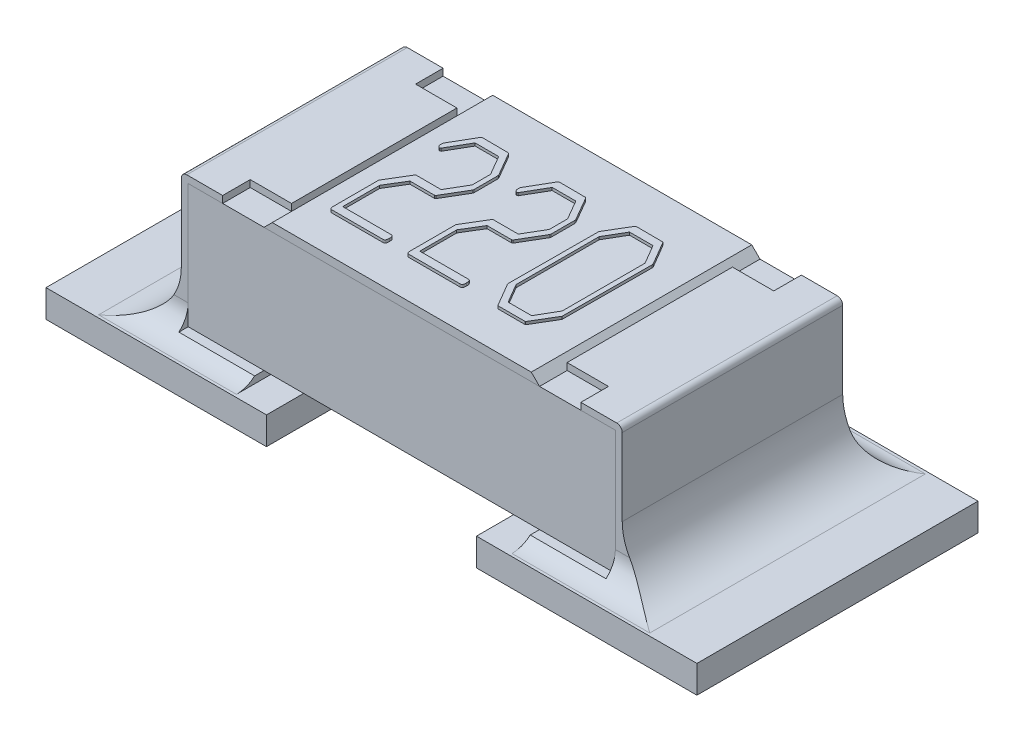
SolidWorks part; units mm, degrees
material "Ceramic Porcelain"
ref_plane "Front Plane" through (0, 0, 0) normal (0, 0, 1) x (1, 0, 0)
ref_plane "Top Plane" through (0, 0, 0) normal (0, 1, 0) x (1, 0, 0)
ref_plane "Right Plane" through (0, 0, 0) normal (1, 0, 0) x (0, 0, -1)
sketch "Sketch1" plane through (0, 0, 0) normal (1, 0, 0) x (0, 0, -1)
  line L0 (0, 55) -> (0, -55) construction
  line L1 (-0.4, 0.575) -> (0.4, 0.575)
  line L2 (-0.4, 0.575) -> (-0.4, 0.125)
  line L3 (-0.4, 0.125) -> (0.4, 0.125)
  line L4 (0.4, 0.575) -> (0.4, 0.125)
  line L5 (55, 0) -> (-55, 0) construction
  dimension "D1" = 0.8
  dimension "D2" = 0.4
  dimension "D3" = 0.45
  dimension "D4" = 0.125
extrude "Boss-Extrude1" add sketch "Sketch1" along normal mid plane 1.55
sketch "Sketch2" plane through (0, 0, 0) normal (0, 0, 1) x (1, 0, 0)
  line L0 (-0.5, 0.6) -> (-0.78, 0.6)
  line L1 (-0.8, 0.58) -> (-0.8, 0.1)
  line L2 (-0.8, 0.1) -> (-0.5, 0.1)
  line L3 (-0.5, 0.1) -> (-0.5, 0.125)
  line L4 (0.775, 0.125) -> (-0.775, 0.125) construction
  line L5 (-0.5, 0.125) -> (-0.775, 0.125)
  line L6 (-0.775, 0.125) -> (-0.775, 0.575)
  line L7 (-0.775, 0.575) -> (-0.5, 0.575)
  line L8 (0.775, 0.575) -> (-0.775, 0.575) construction
  line L9 (-0.5, 0.575) -> (-0.5, 0.6)
  line L11 (0.5, 0.575) -> (0.5, 0.6)
  line L12 (0.5, 0.6) -> (0.78, 0.6)
  line L13 (0.8, 0.58) -> (0.8, 0.1)
  line L14 (0.8, 0.1) -> (0.5, 0.1)
  line L15 (0.5, 0.1) -> (0.5, 0.125)
  line L16 (0.5, 0.125) -> (0.775, 0.125)
  line L17 (0.775, 0.125) -> (0.775, 0.575)
  line L18 (0.775, 0.575) -> (0.5, 0.575)
  arc A0 (0.78, 0.6) -> (0.8, 0.58) centre (0.78, 0.58) cw
  arc A1 (-0.78, 0.6) -> (-0.8, 0.58) centre (-0.78, 0.58) ccw
  point P28 (-0.8, 0.6)
  dimension "D6" = 0.02
  dimension "D1" = 0.025
  dimension "D2" = 0.025
  dimension "D3" = 0.025
  dimension "D4" = 0.3
  dimension "D5" = 0.3
extrude "Boss-Extrude2" add sketch "Sketch2" along normal mid plane 0.8 separate body
sketch "Sketch3" plane through (0, 0.6, 0) normal (0, 1, 0) x (1, 0, 0)
  line L0 (0.5, -0.4) -> (0.5, 0.4) construction
  line L1 (-0.5, 0.4) -> (-0.65, 0.4)
  line L2 (-0.5, 0.4) -> (-0.5, 0.3)
  line L3 (-0.5, 0.3) -> (-0.65, 0.3)
  line L4 (-0.65, 0.4) -> (-0.65, 0.3)
  line L5 (-0.5, -0.4) -> (-0.65, -0.4)
  line L6 (-0.5, -0.4) -> (-0.5, -0.3)
  line L7 (-0.5, -0.3) -> (-0.65, -0.3)
  line L8 (-0.65, -0.4) -> (-0.65, -0.3)
  line L9 (0.5, -0.4) -> (0.65, -0.4)
  line L10 (0.5, -0.4) -> (0.5, -0.3)
  line L11 (0.5, -0.3) -> (0.65, -0.3)
  line L12 (0.65, -0.4) -> (0.65, -0.3)
  line L13 (0.775, -0.4) -> (-0.775, -0.4) construction
  line L15 (0.5, 0.4) -> (0.65, 0.4)
  line L16 (0.5, 0.4) -> (0.5, 0.3)
  line L17 (0.5, 0.3) -> (0.65, 0.3)
  line L18 (0.65, 0.4) -> (0.65, 0.3)
  dimension "D1" = 0.15
  dimension "D2" = 0.1
extrude "Cut-Extrude1" cut sketch "Sketch3" against normal blind 0.025
sketch "Sketch4" plane through (0, 0, 0) normal (0, 0, 1) x (1, 0, 0)
  line L0 (-0.5, 0.575) -> (0.5, 0.575)
  line L1 (0.5, 0.575) -> (0.47, 0.605)
  line L2 (0.47, 0.605) -> (-0.47, 0.605)
  line L3 (-0.47, 0.605) -> (-0.5, 0.575)
  dimension "D1" = 45
  dimension "D2" = 45
  dimension "D3" = 0.03
extrude "Boss-Extrude3" add sketch "Sketch4" along normal mid plane 0.8 separate body
sketch "Sketch6" plane through (0, 0.605, 0) normal (0, 1, 0) x (1, 0, 0)
  line L0 (-0.4, -0.25) -> (0.4, -0.25) construction
  line L1 (0, -0.2777) -> (0, 0.2777) construction
  line L2 (-0.2777, 0) -> (0.2777, 0) construction
  text T0 "220\r\n" font "SWMono" height 0.5
  dimension "D1" = 0.8
  dimension "D2" = 0.4
  dimension "D3" = 0.25
extrude "Boss-Extrude4" add sketch "Sketch6" along normal blind 0.01
sketch "Sketch7" plane through (0, 0, 0) normal (0, 1, 0) x (1, 0, 0)
  line L0 (0, -0.2833) -> (0, 0.2833) construction
  line L1 (-0.381, -0.51) -> (-1.181, -0.51)
  line L2 (-0.381, -0.51) -> (-0.381, 0.51)
  line L3 (-0.381, 0.51) -> (-1.181, 0.51)
  line L4 (-1.181, -0.51) -> (-1.181, 0.51)
  line L5 (0.381, -0.51) -> (1.181, -0.51)
  line L6 (0.381, -0.51) -> (0.381, 0.51)
  line L7 (0.381, 0.51) -> (1.181, 0.51)
  line L8 (1.181, -0.51) -> (1.181, 0.51)
  line L9 (-0.2833, 0) -> (0.2833, 0) construction
  dimension "D1" = 0.8
  dimension "D2" = 0.381
  dimension "D3" = 0.381
  dimension "D4" = 1.02
  dimension "D5" = 0.51
extrude "Boss-Extrude5" add sketch "Sketch7" along normal blind 0.1
fillet "Fillet3" radius 0.2 1 edges at (-0.8, 0.1, 0)
fillet "Fillet4" radius 0.2 1 edges at (0.8, 0.1, 0)
fillet "Fillet5" radius 0.1 2 edges at (0.75, 0.1, -0.4) (0.75, 0.1, 0.4)
fillet "Fillet6" radius 0.1 2 edges at (-0.75, 0.1, 0.4) (-0.75, 0.1, -0.4)
